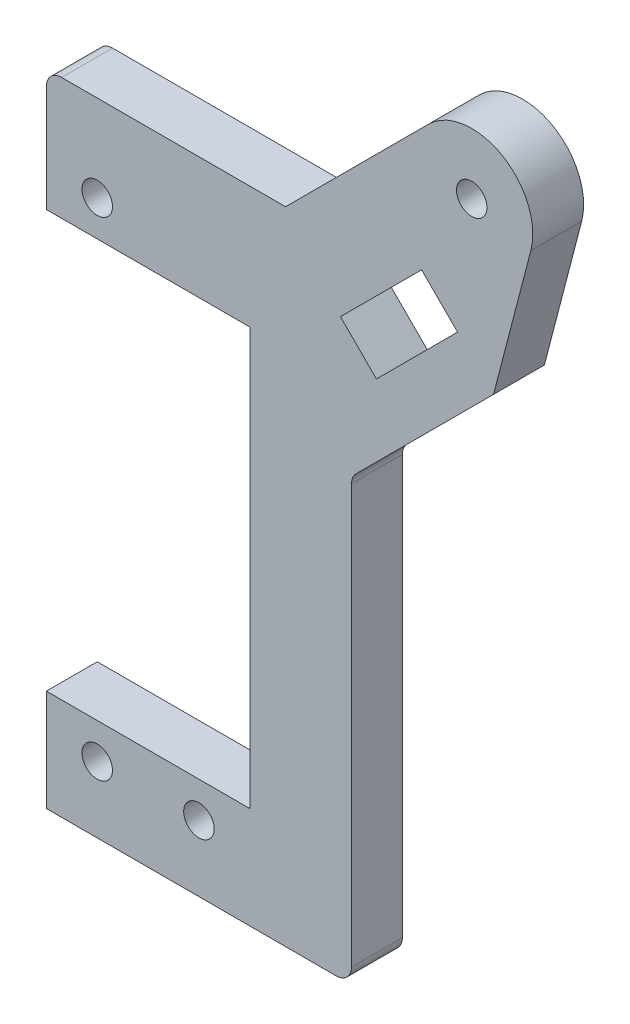
SolidWorks part; units mm, degrees
ref_plane "Plan de face" through (0, 0, 0) normal (0, 0, 1) x (1, 0, 0)
ref_plane "Plan de dessus" through (0, 0, 0) normal (0, 1, 0) x (1, 0, 0)
ref_plane "Plan de droite" through (0, 0, 0) normal (1, 0, 0) x (0, 0, -1)
sketch "Esquisse1" plane through (0, 0, 0) normal (0, 0, 1) x (1, 0, 0)
  line L0 (0, 10) -> (0, 0)
  line L1 (0, 0) -> (30, 0)
  line L2 (10, 10) -> (10, 51) construction
  line L3 (0, 63) -> (23.5147, 63)
  line L4 (36.8905, 64.3141) -> (28.9121, 56.3358)
  line L5 (11, 51) -> (0, 51)
  line L6 (36.8905, 64.3141) -> (40.426, 60.7786)
  line L7 (20, 10) -> (11, 10)
  line L8 (0, 30.5) -> (0, 10)
  line L9 (0, 30.5) -> (20, 30.5) construction
  line L10 (20, 10) -> (20, 51)
  line L11 (20, 51) -> (11, 51)
  line L12 (47.626, 71.307) -> (43.9615, 57.2431)
  line L13 (43.9615, 57.2431) -> (30, 43.2815)
  line L14 (28.9121, 56.3358) -> (32.4476, 52.8002)
  line L15 (32.4476, 52.8002) -> (40.426, 60.7786)
  line L16 (37.5772, 77.0624) -> (23.5147, 63)
  line L18 (11, 10) -> (0, 10)
  line L24 (30, 43.2815) -> (30, 0)
  line L25 (0, 63) -> (0, 51)
  line L26 (40.426, 60.7786) -> (43.9615, 57.2431) construction
  circle A0 centre (5, 54.5) radius 1.5
  circle A1 centre (15, 54.5) radius 1.5 construction
  circle A2 centre (15, 6.5) radius 1.5
  circle A3 centre (5, 6.5) radius 1.5
  circle A4 centre (41.8198, 72.8198) radius 1.5
  circle A5 centre (41.8198, 72.8198) radius 1.725 construction
  arc A6 (37.5772, 77.0624) -> (47.626, 71.307) centre (41.8198, 72.8198) cw
  dimension "D6" = 20
  dimension "D8" = 5
  dimension "D11" = 3
  dimension "D16" = 10
  dimension "D5" = 3
  dimension "D12" = 11.2831
  dimension "D13" = 6
  dimension "D1" = 41
  dimension "D2" = 12
  dimension "D3" = 3.5
  dimension "D4" = 5
  dimension "D7" = 5
  dimension "D14" = 10
extrude "Boss.-Extru.1" add sketch "Esquisse1" along normal blind 5 contours L3 L25 L1 L4 L14 L15 L18 L8 L5 L11 L10 L7 A0 A2 A3 region at (23.7864, 40.598, 0)
fillet "Congé3" radius 1.5 3 edges at (0, 63, 2.5) (30, 0, 2.5) (30, 43.2815, 2.5)
